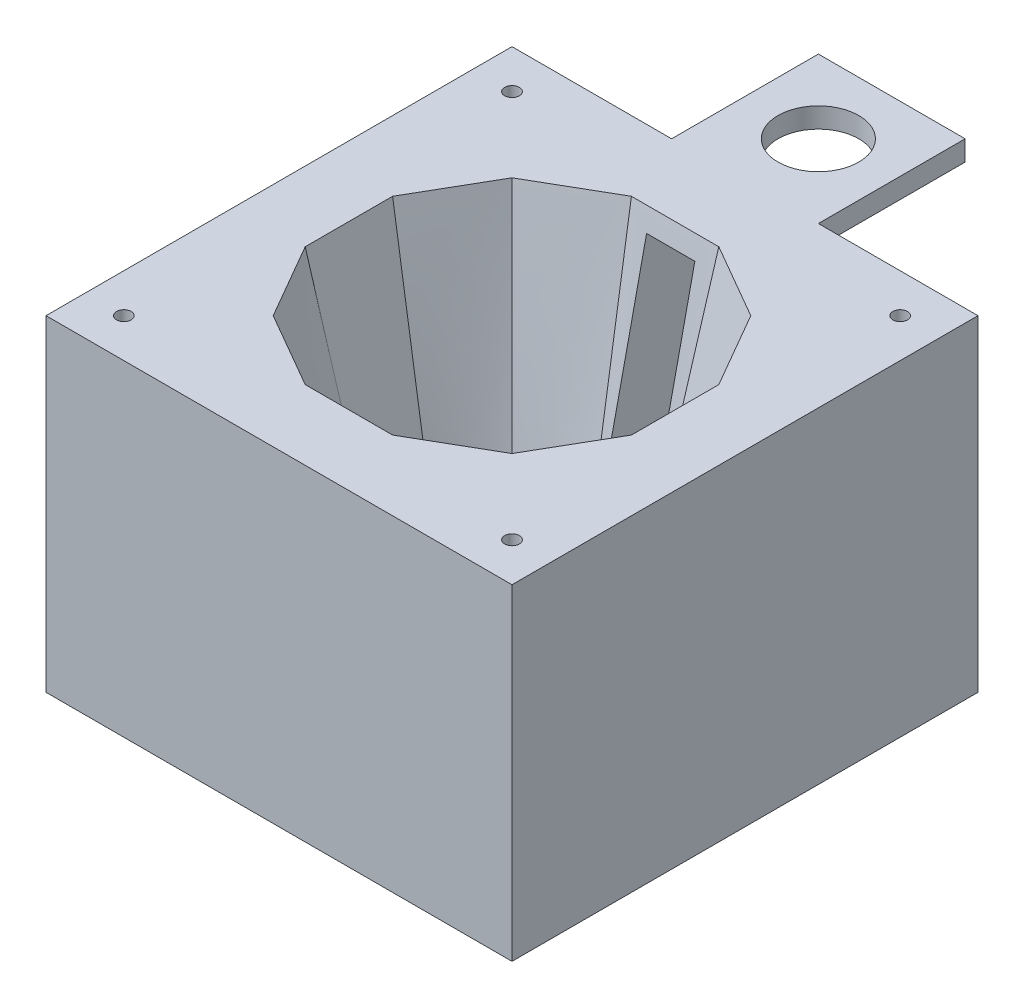
SolidWorks part; units mm, degrees
material "Nylon 101"
ref_plane "Front Plane" through (0, 0, 0) normal (0, 0, 1) x (1, 0, 0)
ref_plane "Top Plane" through (0, 0, 0) normal (0, 1, 0) x (1, 0, 0)
ref_plane "Right Plane" through (0, 0, 0) normal (1, 0, 0) x (0, 0, -1)
sketch "id" plane through (0, 0, 0) normal (0, 1, 0) x (1, 0, 0)
  circle A0 centre (0, 0) radius 25.4
  dimension "D1" = 50.8
ref_plane "Outside face" through (0, 88.9, 0) normal (0, 1, 0) x (1, 0, 0)
sketch "od" plane through (0, 88.9, 0) normal (0, 1, 0) x (1, 0, 0)
  line L1 (44.45, -11.9103) -> (44.45, 11.9103)
  line L2 (44.45, 11.9103) -> (32.5397, 32.5397)
  line L3 (32.5397, 32.5397) -> (11.9103, 44.45)
  line L4 (11.9103, 44.45) -> (-11.9103, 44.45)
  line L5 (-11.9103, 44.45) -> (-32.5397, 32.5397)
  line L6 (-32.5397, 32.5397) -> (-44.45, 11.9103)
  line L7 (-44.45, 11.9103) -> (-44.45, -11.9103)
  line L8 (-44.45, -11.9103) -> (-32.5397, -32.5397)
  line L9 (-32.5397, -32.5397) -> (-11.9103, -44.45)
  line L10 (-11.9103, -44.45) -> (11.9103, -44.45)
  line L11 (11.9103, -44.45) -> (32.5397, -32.5397)
  line L12 (32.5397, -32.5397) -> (44.45, -11.9103)
  circle A0 centre (0, 0) radius 44.45 construction
  dimension "D1" = 88.9
sketch "Sketch3" plane through (0, 88.9, 0) normal (0, 1, 0) x (1, 0, 0)
  line L0 (-48.895, 0) -> (48.895, 0) construction
  line L1 (-63.5, -63.5) -> (63.5, -63.5)
  line L2 (-63.5, -63.5) -> (-63.5, 63.5)
  line L3 (-63.5, 63.5) -> (63.5, 63.5)
  line L4 (63.5, -63.5) -> (63.5, 63.5)
  line L5 (-63.5, -63.5) -> (63.5, 63.5) construction
  line L6 (-63.5, 63.5) -> (63.5, -63.5) construction
  line L7 (0, -48.895) -> (0, 48.895) construction
  circle A0 centre (-52.8934, 52.8934) radius 2
  circle A1 centre (-52.8934, -52.8934) radius 2
  circle A2 centre (52.8934, -52.8934) radius 2
  circle A3 centre (52.8934, 52.8934) radius 2
  point P0 (0, 0)
  point P6 (-53.0546, 53.0546)
  dimension "D2" = 4
  dimension "D1" = 127
  dimension "D3" = 15
extrude "Boss-Extrude1" add sketch "Sketch3" against normal up to surface (88.9 mm away) contours L1 L4 L3 L2 A1 A0 A2 A3 | A1 | A2 | A3 | A0 region at (0, 88.9, 0) region at (-52.8934, 88.9, -52.8934) region at (-52.8934, 88.9, 52.8934) region at (52.8934, 88.9, 52.8934) region at (52.8934, 88.9, -52.8934) up to plane "Top Plane"
extrude "Cut-Extrude1" cut sketch "Sketch3<3>" against normal blind 30 contours A1 | A2 | A3 | A0 region at (-52.8934, 88.9, -52.8934) region at (-52.8934, 88.9, 52.8934) region at (52.8934, 88.9, 52.8934) region at (52.8934, 88.9, -52.8934)
sketch "Sketch3<3>" plane through (0, 88.9, 0) normal (0, 1, 0) x (1, 0, 0) same geometry as "Sketch3"
loft "Cut-Loft1" cut profiles "od", "id" connector at (-32.5397, 88.9, 32.5397) connector at (-6.8408, 0, 24.4615)
sketch "Sketch5" plane through (0, 88.9, 0) normal (0, 1, 0) x (1, 0, 0)
  line L0 (-63.5, 63.5) -> (63.5, 63.5) construction
  line L1 (-6.574, 63.5) -> (6.574, 63.5)
  line L2 (-6.574, 63.5) -> (-6.574, 24.5345)
  line L4 (6.574, 63.5) -> (6.574, 24.5345)
  arc A0 (6.574, 24.5345) -> (-6.574, 24.5345) centre (0, 0) ccw construction
  arc A1 (6.574, 24.5345) -> (-6.574, 24.5345) centre (0, 0) ccw
  point P1 (-6.2113, 24.6288)
  point P9 (6.574, 24.186)
extrude "Cut-Extrude3" cut sketch "Sketch5" against normal through all from offset 5.5 offset against normal yes
sketch "Sketch6" plane through (0, 88.9, 0) normal (0, 1, 0) x (1, 0, 0)
  line L0 (-63.5, 63.5) -> (63.5, 63.5) construction
  line L1 (-20, 63.5) -> (20, 63.5)
  line L2 (-20, 63.5) -> (-20, 103.5)
  line L3 (-20, 103.5) -> (20, 103.5)
  line L4 (20, 63.5) -> (20, 103.5)
  circle A0 centre (0, 83.5) radius 11
  point P9 (0, 103.5)
  point P10 (24.8822, 63.5)
  point P11 (0, 0)
  point P12 (0, 0)
  point P13 (-20, 83.5)
  dimension "D1" = 22
  dimension "D2" = 40
extrude "Boss-Extrude2" add sketch "Sketch6" against normal up to surface (5.5 mm away) up to face at (0, 83.4, -53.3813)
equation "\"id\"= 2in"
equation "\"od\"= 4in"
equation "\"h\"= 3.5in"
equation "\"D1@id\" = \"id\""
equation "\"D1@od\" = \"h\""
